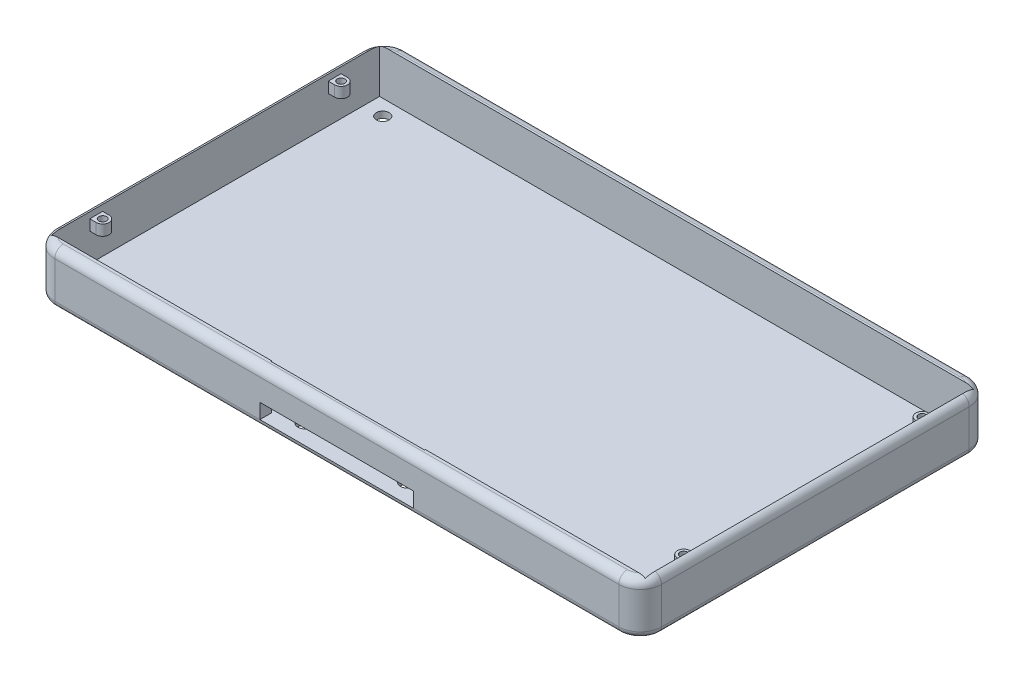
SolidWorks part; units mm, degrees
ref_plane "前视基准面" through (0, 0, 0) normal (0, 0, 1) x (1, 0, 0)
ref_plane "上视基准面" through (0, 0, 0) normal (0, 1, 0) x (1, 0, 0)
ref_plane "右视基准面" through (0, 0, 0) normal (1, 0, 0) x (0, 0, -1)
sketch "草图1" plane through (0, 0, 0) normal (0, 1, 0) x (1, 0, 0)
  line L1 (0, 0) -> (142, 0)
  line L2 (0, 0) -> (0, -82)
  line L3 (0, -82) -> (142, -82)
  line L4 (142, 0) -> (142, -82)
  dimension "D1" = 142
  dimension "D2" = 82
extrude "凸台-拉伸1" add sketch "草图1" along normal blind 12.1 contours L1 L4 L3 L2
shell "抽壳1" thickness 1.5 removed face at (71, 12.1, 41)
sketch "草图2" plane through (0, 1.5, 0) normal (0, 1, 0) x (1, 0, 0)
  line L0 (59, -77.5) -> (1.5, -77.5) construction
  line L1 (1.5, -1.5) -> (1.5, -80.5) construction
  line L2 (83, -77.5) -> (140.5, -77.5) construction
  line L3 (140.5, -1.5) -> (140.5, -80.5) construction
  line L4 (0, -82) -> (142, -82) construction
  circle A0 centre (83, -77.5) radius 1.6
  circle A1 centre (59, -77.5) radius 1.6
  dimension "D1" = 3.2
  dimension "D2" = 24
  dimension "5" = 4.5
extrude "切除-拉伸1" cut sketch "草图2" against normal blind 15
sketch "草图4" plane through (0, 1.5, 0) normal (0, 1, 0) x (1, 0, 0)
  line L0 (5.9, -75.85) -> (1.5, -75.85) construction
  line L1 (1.5, -1.5) -> (1.5, -80.5) construction
  line L2 (5.9, -75.85) -> (5.9, -1.5) construction
  line L3 (1.5, -1.5) -> (140.5, -1.5) construction
  line L4 (5.9, -6.15) -> (1.5, -6.15) construction
  line L5 (1.5, -1.5) -> (1.5, -80.5) construction
  line L6 (136.1, -75.85) -> (136.1, -1.5) construction
  line L7 (1.5, -1.5) -> (140.5, -1.5) construction
  line L8 (5.9, -6.15) -> (5.9, -80.5) construction
  line L9 (1.5, -80.5) -> (140.5, -80.5) construction
  line L10 (136.1, -6.15) -> (136.1, -80.5) construction
  line L11 (136.1, -75.85) -> (140.5, -75.85) construction
  line L12 (140.5, -1.5) -> (140.5, -80.5) construction
  line L13 (136.1, -6.15) -> (140.5, -6.15) construction
  circle A0 centre (5.9, -75.85) radius 1.5
  circle A1 centre (136.1, -75.85) radius 1.5
  circle A2 centre (5.9, -6.15) radius 1.5
  circle A3 centre (136.1, -6.15) radius 1.5
  dimension "D1" = 3
  dimension "D2" = 130.2
  dimension "D3" = 69.7
extrude "切除-拉伸2" cut sketch "草图4" against normal blind 15
sketch "草图5" plane through (0, 0, 82) normal (0, 0, 1) x (1, 0, 0)
  line L0 (0, 0) -> (142, 0) construction
  line L1 (53, 5) -> (89, 5)
  line L2 (53, 5) -> (53, 1.5)
  line L3 (53, 1.5) -> (89, 1.5)
  line L4 (89, 5) -> (89, 1.5)
  line L5 (53, 3.25) -> (0, 3.25) construction
  line L6 (0, 12.1) -> (0, 0) construction
  line L7 (89, 3.25) -> (142, 3.25) construction
  line L8 (142, 12.1) -> (142, 0) construction
  dimension "D1" = 36
  dimension "D2" = 3.5
  dimension "D3" = 1.5
extrude "切除-拉伸3" cut sketch "草图5" against normal blind 15
ref_plane "基准面4" through (0, 8.1, 0) normal (0, 1, 0) x (1, 0, 0)
sketch "草图6" plane through (0, 8.1, 0) normal (0, 1, 0) x (1, 0, 0)
  line L0 (1.5, -67.3) -> (4.5, -67.3)
  line L1 (1.5, -11.5) -> (4.5, -11.5)
  line L2 (1.5, -11.5) -> (1.5, -14.5)
  line L3 (1.5, -14.5) -> (4.5, -14.5)
  line L4 (4.5, -11.5) -> (4.5, -14.5)
  line L5 (1.5, -67.3) -> (1.5, -70.3)
  line L6 (1.5, -70.3) -> (4.5, -70.3)
  line L7 (4.5, -67.3) -> (4.5, -70.3)
  line L8 (137.5, -11.5) -> (140.5, -11.5)
  line L9 (137.5, -11.5) -> (137.5, -14.5)
  line L10 (137.5, -14.5) -> (140.5, -14.5)
  line L11 (140.5, -11.5) -> (140.5, -14.5)
  line L12 (137.5, -67.3) -> (140.5, -67.3)
  line L13 (137.5, -67.3) -> (137.5, -70.3)
  line L14 (137.5, -70.3) -> (140.5, -70.3)
  line L15 (140.5, -67.3) -> (140.5, -70.3)
  line L16 (140.5, -1.5) -> (140.5, -80.5) construction
  line L17 (1.5, -1.5) -> (140.5, -1.5) construction
  line L18 (1.5, -1.5) -> (1.5, -80.5) construction
  line L20 (1.5, -80.5) -> (53, -80.5) construction
  line L21 (1.5, -80.5) -> (140.5, -80.5) construction
  line L22 (1.5, -1.5) -> (140.5, -1.5) construction
  dimension "D1" = 3
  dimension "D2" = 3
  dimension "D3" = 3
  dimension "D4" = 0
  dimension "D5" = 3
  dimension "D6" = 0
  dimension "D7" = 10
  dimension "D8" = 10.2
  dimension "D9" = 3
  dimension "D10" = 10.2
  dimension "D11" = 10
extrude "凸台-拉伸2" add sketch "草图6" along normal blind 2.5
sketch "草图7" plane through (0, 10.6, 0) normal (0, 1, 0) x (1, 0, 0)
  line L0 (4.5, -11.5) -> (1.5, -11.5) construction
  line L1 (1.5, -11.5) -> (1.5, -14.5) construction
  line L2 (1.5, -70.3) -> (4.5, -70.3) construction
  line L3 (140.5, -1.5) -> (140.5, -80.5) construction
  line L4 (1.5, -1.5) -> (140.5, -1.5) construction
  circle A0 centre (3, -13) radius 0.9
  circle A1 centre (3, -68.8) radius 0.9024
  circle A2 centre (139, -68.8) radius 0.9
  circle A3 centre (139, -13) radius 0.9
  dimension "D1" = 1.8
  dimension "D5" = 1.8048
  dimension "D7" = 1.8
  dimension "D8" = 1.8
  dimension "D2" = 1.5
  dimension "D3" = 1.5
  dimension "D4" = 1.5
  dimension "D6" = 1.5
  dimension "D9" = 11.5
extrude "切除-拉伸4" cut sketch "草图7" against normal up to next
fillet "圆角4" 2 edges at (4.5, 9.35, 14.5) (4.5, 9.35, 11.5) type full round first side face at (3, 9.35, 14.5) second side face at (3, 9.35, 11.5) middle face at (4.5, 9.35, 13)
fillet "圆角5" 2 edges at (4.5, 9.35, 67.3) (4.5, 9.35, 70.3) type full round first side face at (3, 9.35, 67.3) second side face at (3, 9.35, 70.3) middle face at (4.5, 9.35, 68.8)
fillet "圆角6" 2 edges at (137.5, 9.35, 11.5) (137.5, 9.35, 14.5) type full round first side face at (139, 9.35, 11.5) second side face at (139, 9.35, 14.5) middle face at (137.5, 9.35, 13)
fillet "圆角7" 2 edges at (137.5, 9.35, 67.3) (137.5, 9.35, 70.3) type full round first side face at (139, 9.35, 67.3) second side face at (139, 9.35, 70.3) middle face at (137.5, 9.35, 68.8)
fillet "圆角8" radius 5 4 edges at (0, 6.05, 82) (0, 6.05, 0) (142, 6.05, 0) (142, 6.05, 82)
fillet "圆角13" radius 1.5 8 edges at (1.4645, 0, 1.4645) (71, 0, 0) (140.5355, 0, 1.4645) (142, 0, 41) (140.5355, 0, 80.5355) (71, 0, 82) (1.4645, 0, 80.5355) (0, 0, 41)
sketch "草图8" plane through (0, 12.1, 0) normal (0, 1, 0) x (1, 0, 0)
  line L0 (1.5, -1.5) -> (140.5, -1.5) construction
  line L1 (1.5, -1.5) -> (140.5, -1.5)
  line L2 (1.5, -1.5) -> (1.5, -2.5)
  line L3 (1.5, -2.5) -> (140.5, -2.5)
  line L4 (140.5, -1.5) -> (140.5, -2.5)
  line L5 (1.5, -1.5) -> (1.5, -80.5) construction
  line L6 (140.5, -1.5) -> (140.5, -80.5) construction
  dimension "D1" = 1
  dimension "D2" = 0
  dimension "D3" = 0
  dimension "D4" = 0
extrude "凸台-拉伸7" add sketch "草图8" against normal up to surface (10.6 mm away) up to face at (71, 1.5, 61.125)
sketch "草图9" plane through (0, 12.1, 0) normal (0, 1, 0) x (1, 0, 0)
  line L0 (53, -80.5) -> (53, -82) construction
  line L1 (53, -79.5) -> (89, -79.5)
  line L2 (53, -79.5) -> (53, -80.5)
  line L3 (53, -80.5) -> (89, -80.5)
  line L4 (89, -79.5) -> (89, -80.5)
  line L5 (89, -80.5) -> (89, -82) construction
  line L6 (1.5, -80.5) -> (140.5, -80.5) construction
  dimension "D1" = 1
  dimension "D2" = 0
  dimension "D3" = 0
  dimension "D4" = 0
extrude "凸台-拉伸8" add sketch "草图9" against normal up to surface (7.1 mm away) up to face at (71, 5, 81.25)
sketch "草图10" plane through (0, 12.1, 0) normal (0, 1, 0) x (1, 0, 0)
  line L0 (140.5, -2.5) -> (140.5, -80.5) construction
  line L1 (1.5, -80.5) -> (53, -80.5)
  line L2 (1.5, -80.5) -> (1.5, -79.3)
  line L3 (1.5, -79.3) -> (53, -79.3)
  line L4 (53, -80.5) -> (53, -79.3)
  line L5 (89, -80.5) -> (140.5, -80.5)
  line L6 (89, -80.5) -> (89, -79.3)
  line L7 (89, -79.3) -> (140.5, -79.3)
  line L8 (140.5, -80.5) -> (140.5, -79.3)
  dimension "D1" = 1.2
extrude "凸台-拉伸9" add sketch "草图10" against normal up to surface (10.6 mm away) up to face at (71, 1.5, 61.375)
fillet "圆角14" radius 2 8 edges at (1.4645, 12.1, 80.5355) (0, 12.1, 41) (1.4645, 12.1, 1.4645) (71, 12.1, 0) (140.5355, 12.1, 1.4645) (142, 12.1, 41) (140.5355, 12.1, 80.5355) (71, 12.1, 82)
sketch "草图11" plane through (0, 0, 0) normal (0, -1, 0) x (1, 0, 0)
  line L0 (51, 48) -> (51, 80.5) construction
  line L1 (51, 48) -> (91, 48)
  line L2 (51, 48) -> (51, 34)
  line L3 (51, 34) -> (91, 34)
  line L4 (91, 48) -> (91, 34)
  line L5 (137, 80.5) -> (5, 80.5) construction
  line L6 (51, 48) -> (1.5, 48) construction
  line L7 (1.5, 77) -> (1.5, 5) construction
  line L8 (91, 34) -> (91, 1.5) construction
  line L9 (5, 1.5) -> (137, 1.5) construction
  line L10 (91, 34) -> (140.5, 34) construction
  line L11 (140.5, 5) -> (140.5, 77) construction
  dimension "D1" = 14
  dimension "D2" = 40
extrude "切除-拉伸5" cut sketch "草图11" against normal blind 0.2
fillet "圆角15" radius 5 1 edges at (51, 0.1, 48) type face fillet first side face at (71, 0.1, 48) second side face at (51, 0.1, 41)
fillet "圆角16" radius 5 1 edges at (51, 0.1, 34) type face fillet first side face at (51, 0.1, 38.5) second side face at (71, 0.1, 34)
fillet "圆角17" radius 5 1 edges at (91, 0.1, 48) type face fillet first side face at (73.5, 0.1, 48) second side face at (91, 0.1, 41)
fillet "圆角18" radius 5 1 edges at (91, 0.1, 34) type face fillet first side face at (91, 0.1, 38.5) second side face at (73.5, 0.1, 34)
sketch "草图12" plane through (0, 0.2, 0) normal (0, -1, 0) x (1, 0, 0)
  line L0 (81, 39.5) -> (45.9558, 39.5) construction
  text T0 "Dimsmary x\r\nUiharu Kazari" font "Century Gothic" height 2.5
  point P3 (61.7882, 42.3246)
  point P4 (60.658, 42.2438)
  point P5 (0, 0)
  point P6 (0, 0)
  point P7 (63.2413, 42.0686)
  point P8 (46.0191, 43.5475)
  point P9 (79.6417, 41.8822)
  point P10 (81.3701, 40.6649)
  point P11 (0, 0)
  point P12 (0, 0)
  point P13 (81.7225, 38.2041)
  point P14 (81.4574, 40.3733)
  point P15 (0, 0)
  point P16 (0, 0)
extrude "凸台-拉伸10" add sketch "草图12" along normal blind 0.2
